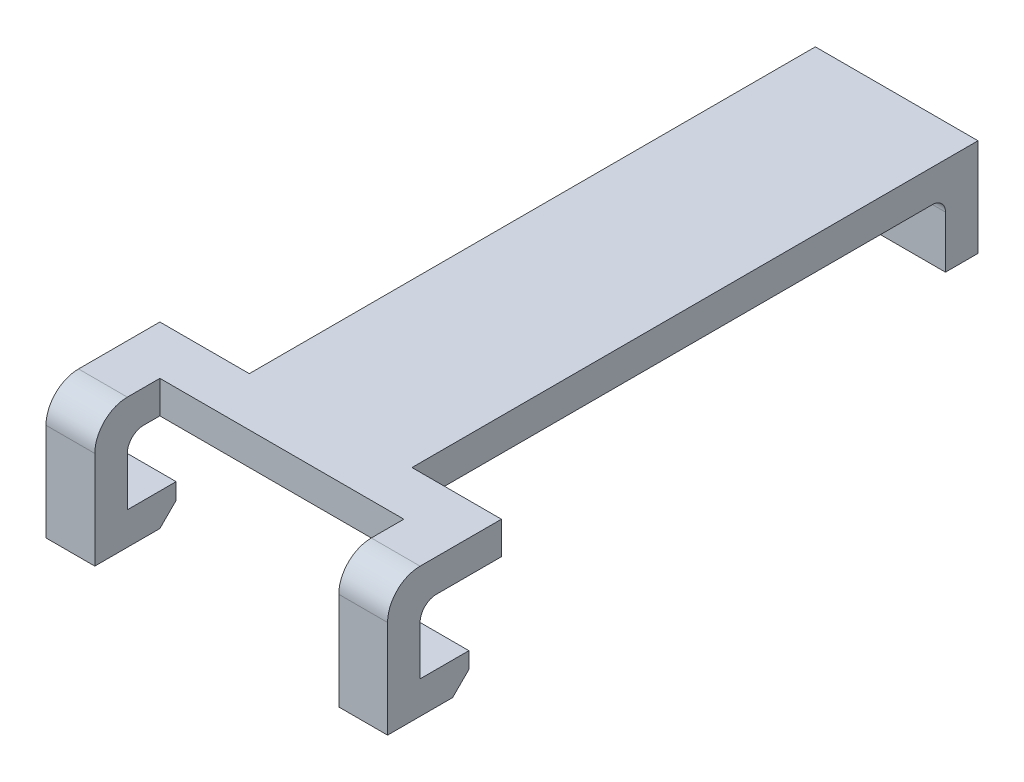
SolidWorks part; units mm, degrees
ref_plane "Front Plane" through (0, 0, 0) normal (0, 0, 1) x (1, 0, 0)
ref_plane "Top Plane" through (0, 0, 0) normal (0, 1, 0) x (1, 0, 0)
ref_plane "Right Plane" through (0, 0, 0) normal (1, 0, 0) x (0, 0, -1)
sketch "Sketch1" plane through (0, 0, 0) normal (0, 1, 0) x (1, 0, 0)
  line L0 (-5, -15.9) -> (-10.5, -15.9)
  line L1 (-5, 18.9) -> (5, 18.9)
  line L2 (-5, 18.9) -> (-5, -18.9)
  line L3 (-5, -18.9) -> (5, -18.9)
  line L4 (5, 18.9) -> (5, -18.9)
  line L5 (-5, 18.9) -> (5, -18.9) construction
  line L6 (-5, -18.9) -> (5, 18.9) construction
  line L7 (-10.5, -15.9) -> (-10.5, -18.9)
  line L8 (-10.5, -18.9) -> (-5, -18.9)
  line L9 (0, 18.9) -> (0, -18.9) construction
  line L10 (10.5, -18.9) -> (5, -18.9)
  line L11 (10.5, -15.9) -> (10.5, -18.9)
  line L12 (5, -15.9) -> (10.5, -15.9)
  point P0 (0, 0)
  point P12 (0, 0)
  dimension "D1" = 37.8
  dimension "D2" = 10
  dimension "D3" = 5.5
  dimension "D4" = 3
extrude "Boss-Extrude1" add sketch "Sketch1" along normal mid plane 2 contours L4 L1 L2 L3 | L7 L8 L2 L0 | L12 L4 L10 L11 region at (-7.75, 0, 17.4) region at (0, 0, 0) region at (7.75, 0, 17.4)
sketch "Sketch2" plane through (0, -1, 0) normal (0, -1, 0) x (1, 0, 0)
  line L1 (-5, -18.9) -> (5, -18.9)
  line L2 (-5, -18.9) -> (-5, -16.9)
  line L3 (-5, -16.9) -> (5, -16.9)
  line L4 (5, -18.9) -> (5, -16.9)
  line L5 (5, -18.9) -> (5, 15.9) construction
  dimension "D1" = 2
extrude "Boss-Extrude2" add sketch "Sketch2" along normal blind 4
ref_plane "Lipare keski" through (0, 0, -17.9) normal (0, 0, 1) x (1, 0, 0)
sketch "Sketch3" plane through (0, 0, 0) normal (1, 0, 0) x (0, 0, -1)
  line L3 (-18.9, -7) -> (-22.9, -7)
  line L4 (-22.9, -7) -> (-22.9, -1)
  line L5 (-20.9, 1) -> (-18.9, 1)
  line L7 (-17.9, -5) -> (-20.9, -5)
  line L8 (-17.9, -5) -> (-17.9, -6)
  line L9 (-17.9, -6) -> (-18.9, -7)
  line L10 (-20.9, -2) -> (-20.9, -5)
  line L12 (-15.9, -1) -> (-18.9, -1) construction
  line L13 (-15.9, 1) -> (-18.9, 1) construction
  line L14 (-19.9, -1) -> (-18.9, -1)
  line L15 (-18.9, 1) -> (-18.9, -1)
  arc A0 (-22.9, -1) -> (-20.9, 1) centre (-20.9, -1) cw
  arc A2 (-19.9, -1) -> (-20.9, -2) centre (-19.9, -2) ccw
  dimension "D2" = 2
  dimension "D1" = 1
  dimension "D3" = 3
  dimension "D4" = 2
  dimension "D5" = 135
  dimension "D6" = 1
  dimension "D7" = 6
  dimension "D8" = 1
extrude "Boss-Extrude3" add sketch "Sketch3" along normal blind 3 from surface starting at face at (-10.5, 0, 17.4)
extrude "Boss-Extrude4" add sketch "Sketch3<3>" against normal blind 3 from surface starting at face at (10.5, 0, 17.4)
sketch "Sketch3<3>" plane through (0, 0, 0) normal (1, 0, 0) x (0, 0, -1) same geometry as "Sketch3"
fillet "Fillet1" radius 0.8 1 edges at (0, -1, -16.9)
sketch "Sketch4" plane through (0, 0, 0) normal (1, 0, 0) x (0, 0, -1)
  line L0 (-20.9, -3.5) -> (-22.9, -3.5) construction
  line L1 (-20.9, -2) -> (-20.9, -5) construction
  line L2 (-22.9, -7) -> (-22.9, -1) construction
  line L3 (-18.4, -1) -> (-18.4, 1) construction
  line L4 (-15.9, -1) -> (-19.9, -1) construction
  line L5 (-15.9, 1) -> (-20.9, 1) construction
  line L6 (-18.4, 1) -> (-20.9, 1)
  line L7 (-22.9, -3.5) -> (-22.9, -1)
  line L8 (-22.9, -3.5) -> (-23.9, -2.5)
  line L9 (-23.9, -2.5) -> (-23.9, -1)
  line L10 (-19.4, 2) -> (-20.9, 2)
  line L11 (-17.4, 2) -> (-20.9, 2) construction
  line L12 (-20.9, -4.5) -> (-23.9, -4.5) construction
  line L13 (-18.4, 1) -> (-19.4, 2)
  line L14 (-23.9, -4.5) -> (-23.9, -1) construction
  line L15 (-17.4, -1) -> (-17.4, 2) construction
  arc A0 (-20.9, 1) -> (-22.9, -1) centre (-20.9, -1) ccw construction
  arc A1 (-20.9, 1) -> (-22.9, -1) centre (-20.9, -1) ccw
  arc A2 (-20.9, 2) -> (-23.9, -1) centre (-20.9, -1) ccw
  dimension "D1" = 1.5
  dimension "D2" = 1.5
  dimension "D4" = 45
  dimension "D5" = 45
  dimension "D3" = 1
